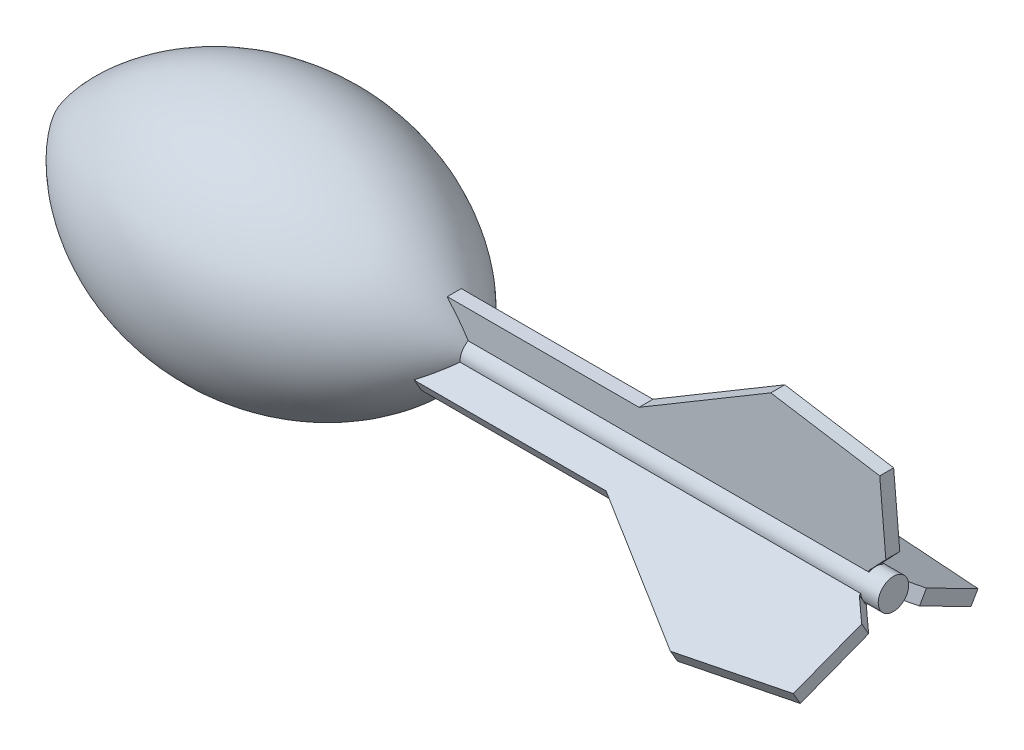
SolidWorks part; units mm, degrees
ref_plane "Front Plane" through (0, 0, 0) normal (0, 0, 1) x (1, 0, 0)
ref_plane "Top Plane" through (0, 0, 0) normal (0, 1, 0) x (1, 0, 0)
ref_plane "Right Plane" through (0, 0, 0) normal (1, 0, 0) x (0, 0, -1)
sketch "Sketch1" plane through (0, 0, 0) normal (0, 1, 0) x (1, 0, 0)
  line L0 (-152.4, 0) -> (152.4, 0) construction
  line L1 (152.4, 0) -> (152.4, 5.5563)
  line L2 (152.4, 5.5563) -> (0, 5.5562)
  line L3 (-152.4, 0) -> (0, 0)
  line L5 (0, 0) -> (152.4, 0)
  arc A0 (0, 5.5562) -> (-152.4, 0) centre (-74.4149, -46.1853) ccw
  dimension "D4" = 88.9
  dimension "D1" = 304.8
  dimension "D2" = 11.1125
  dimension "D3" = 152.4
revolve "Revolve1" add sketch "Sketch1" angle 360 about L0
sketch "Sketch2" plane through (0, 0, 0) normal (0, 0, 1) x (1, 0, 0)
  line L0 (152.4, 5.5562) -> (0, 5.5562) construction
  line L1 (146.05, 5.5563) -> (0, 5.5562)
  line L2 (-7.6229, 15.0812) -> (62.2271, 15.0812)
  line L3 (62.2271, 15.0812) -> (110.2484, 43.6562)
  line L4 (110.2484, 43.6562) -> (149.9359, 37.3063)
  line L5 (149.9359, 37.3063) -> (152.1696, 12.0047)
  line L6 (152.1696, 12.0047) -> (146.05, 5.5563)
  line L7 (-7.6229, 15.0812) -> (-7.6229, 0)
  line L8 (-7.6229, 0) -> (146.05, 0)
  line L9 (146.05, 0) -> (146.05, 5.5563)
  arc A0 (0, 5.5562) -> (-152.4, 0) centre (-74.4149, -46.1853) ccw construction
  arc A1 (0, 5.5562) -> (-7.6229, 15.0812) centre (-74.4149, -46.1853) ccw
  dimension "D1" = 6.35
  dimension "D2" = 9.525
  dimension "D3" = 69.85
  dimension "D4" = 38.1
  dimension "D5" = 31.75
  dimension "D6" = 55.88
  dimension "D7" = 39.6875
  dimension "D8" = 25.4
  dimension "D9" = 8.89
extrude "Boss-Extrude1" add sketch "Sketch2" along normal mid plane 5.08 separate body contours A1 L1 L6 L5 L4 L3 L2 | L1 A1 L7 L8 L9 region at (66.0524, 3.0347, 0) region at (96.0471, 19.0756, 0)
ref_axis "Axis1" through (152.4, 0, 0) along (-1, 0, 0)
ref_plane "Plane1" through (0, 0, 0) normal (0, -0.866, 0.5) x (-1, 0, 0)
ref_plane "Plane2" through (0, 0, 0) normal (0, 0.866, 0.5) x (-1, 0, 0)
sketch "Sketch4" plane through (0, 0, 0) normal (0, 0.866, 0.5) x (-1, 0, 0)
  line L9 (0, 5.5563) -> (-152.4, 5.5562) construction
  line L10 (0, 5.5563) -> (-146.05, 5.5562)
  line L11 (7.7396, 15.2082) -> (-62.1104, 15.2082)
  line L12 (-62.1104, 15.2082) -> (-110.207, 43.6562)
  line L13 (-110.207, 43.6562) -> (-149.2777, 37.0576)
  line L14 (-149.2777, 37.0576) -> (-152.3362, 11.8424)
  line L15 (-152.3362, 11.8424) -> (-146.05, 5.5562)
  line L16 (7.7396, 15.2082) -> (7.7396, 0)
  line L17 (7.7396, 0) -> (-146.05, 0)
  line L18 (-146.05, 0) -> (-146.05, 5.5562)
  arc A1 (152.4, 0) -> (0, 5.5563) centre (74.4149, -46.1853) ccw construction
  arc A2 (7.7396, 15.2082) -> (0, 5.5563) centre (74.4149, -46.1853) ccw
  dimension "D8" = 9.652
  dimension "D9" = 69.85
  dimension "D10" = 55.88
  dimension "D11" = 39.624
  dimension "D12" = 6.35
  dimension "D13" = 38.1
  dimension "D14" = 8.89
  dimension "D15" = 25.4
  dimension "D16" = 45
extrude "Boss-Extrude2" add sketch "Sketch4" along normal mid plane 5.08 contours A2 L11 L12 L13 L14 L15 L10 | L16 A2 L10 L18 L17 region at (65.9065, -1.5218, 2.6359) region at (95.6405, -9.5007, 16.4557)
sketch "Sketch7" plane through (0, 0, 0) normal (0, -0.866, 0.5) x (-1, 0, 0)
  line L0 (0, 5.7407) -> (-146.456, 5.7407)
  line L1 (7.3336, 15.3927) -> (-62.5164, 15.3927)
  line L2 (-62.5164, 15.3927) -> (-110.613, 43.8407)
  line L3 (-110.613, 43.8407) -> (-149.6837, 37.2421)
  line L4 (-149.6837, 37.2421) -> (-152.7421, 12.0269)
  line L5 (-152.7421, 12.0269) -> (-146.456, 5.7407)
  line L6 (7.3336, 15.3927) -> (7.3336, 0.0304)
  line L7 (7.3336, 0.0304) -> (-146.456, 0.0304)
  line L8 (-146.456, 0.0304) -> (-146.456, 5.7407)
  arc A0 (7.3336, 15.3927) -> (0, 5.7407) centre (75.6725, -44.1435) ccw
  dimension "D1" = 9.652
  dimension "D2" = 69.85
  dimension "D3" = 55.88
  dimension "D4" = 39.624
  dimension "D5" = 38.1
  dimension "D6" = 8.89
  dimension "D7" = 25.4
  dimension "D8" = 45
extrude "Boss-Extrude3" add sketch "Sketch7" along normal mid plane 5.08 contours A0 L1 L2 L3 L4 L5 L0 | L6 A0 L0 L8 L7 region at (66.551, -1.5671, -2.7143) region at (95.9828, -9.5897, -16.6098)
ref_plane "CG" through (-51.74, 0, 0) normal (1, 0, 0) x (0, 0, -1)
ref_plane "Plane4" through (0, 44.45, 0) normal (0, 1, 0) x (1, 0, 0)
ref_plane "Plane5" through (0, -44.45, 0) normal (0, 1, 0) x (1, 0, 0)
ref_plane "Plane6" through (0, 0, 44.45) normal (0, 0, 1) x (1, 0, 0)
ref_plane "Plane7" through (0, 0, -44.45) normal (0, 0, 1) x (1, 0, 0)
